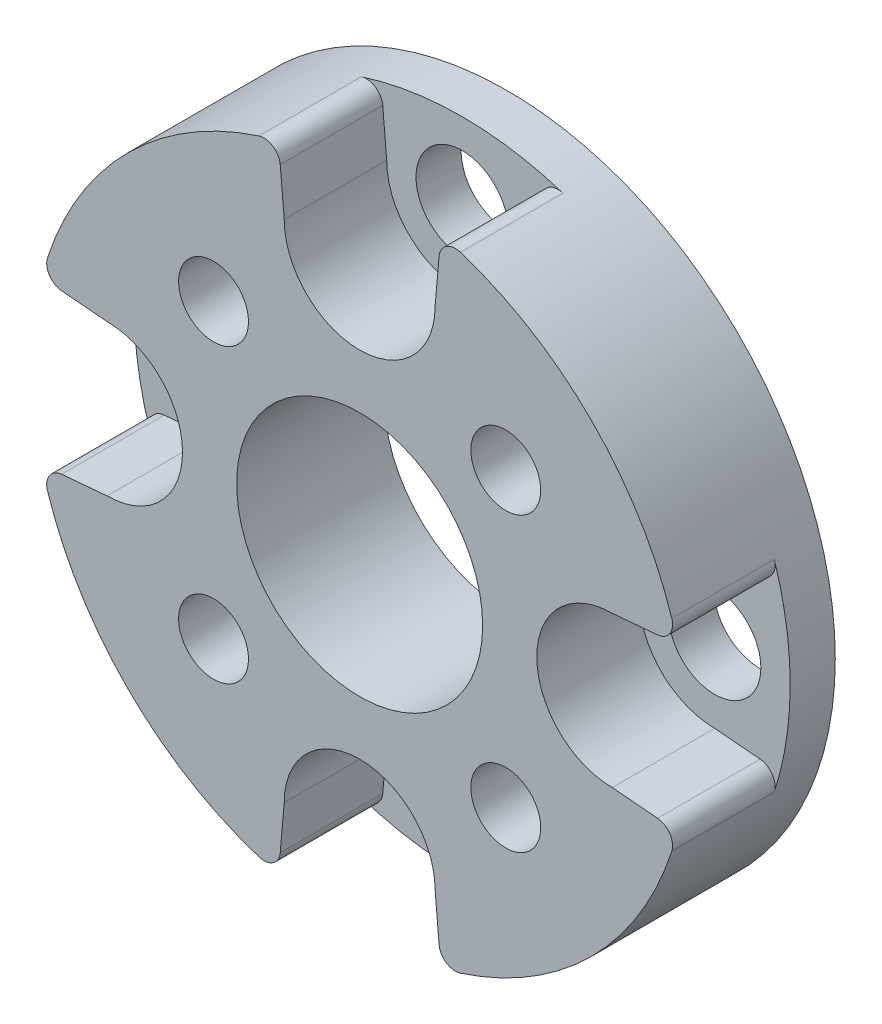
SolidWorks part; units mm, degrees
material "6061 Alloy"
ref_plane "Front Plane" through (0, 0, 0) normal (0, 0, 1) x (1, 0, 0)
ref_plane "Top Plane" through (0, 0, 0) normal (0, 1, 0) x (1, 0, 0)
ref_plane "Right Plane" through (0, 0, 0) normal (1, 0, 0) x (0, 0, -1)
sketch "Sketch1" plane through (0, 0, 0) normal (0, 0, 1) x (1, 0, 0)
  circle A0 centre (0, 0) radius 12.7
  circle A1 centre (0, 0) radius 4.7625
  dimension "D1" = 25.4
  dimension "D2" = 9.525
extrude "Boss-Extrude1" add sketch "Sketch1" along normal mid plane 5.715
hole_wizard "#6-32 Tapped Hole1" positions "Sketch4" profile "Sketch3" tap size "#6-32" standard "Ansi Inch" end condition up to next
sketch "Sketch4" plane through (0, 0, 2.8575) normal (0, 0, 1) x (1, 0, 0)
  line L0 (0, 0) -> (5.6569, 5.6569) construction
  line L2 (0, 0) -> (9.779, 0) construction
  point P0 (5.6569, 5.6569)
  point P19 (5.6569, -5.6569)
  point P20 (-5.6569, -5.6569)
  point P21 (-5.6569, 5.6569)
  dimension "D1" = 8
  dimension "D2" = 45
  dimension "D3" = 9.779
  dimension "D4" = 4
sketch "Sketch3" plane through (5.6569, 5.6569, 2.8575) normal (1, 0, 0) x (0, -1, 0)
  line L0 (0, 0) -> (0, 5.715)
  line L1 (0, 5.715) -> (1.3525, 5.715)
  line L2 (1.3525, 5.715) -> (1.3525, 0)
  line L5 (1.3525, 0) -> (0, 0)
  line L11 (0, -6.35) -> (0, 107.95) construction
  dimension "Thru Tap Drill Dia." = 2.7051
  dimension "Thru Tap Drill Depth" = 5.715
cosmetic thread "Hole Thread1" parameters "D2"=3.5052
cosmetic thread "Hole Thread2" parameters "D2"=3.5052
cosmetic thread "Hole Thread3" parameters "D2"=3.5052
cosmetic thread "Hole Thread4" parameters "D2"=3.5052
sketch "Sketch5" plane through (0, 0, 2.8575) normal (0, 0, 1) x (1, 0, 0)
  line L0 (0, 0) -> (9.779, 0) construction
  line L1 (9.779, 2.921) -> (12.3052, 3.142)
  line L2 (9.779, -2.921) -> (12.3052, -3.142)
  line L3 (2.921, -9.779) -> (3.142, -12.3052)
  line L4 (-2.921, -9.779) -> (-3.142, -12.3052)
  line L5 (-9.779, -2.921) -> (-12.3052, -3.142)
  line L6 (-9.779, 2.921) -> (-12.3052, 3.142)
  line L7 (-2.921, 9.779) -> (-3.142, 12.3052)
  line L8 (2.921, 9.779) -> (3.142, 12.3052)
  arc A0 (9.779, 2.921) -> (9.779, -2.921) centre (9.779, 0) ccw
  circle A1 centre (0, 0) radius 12.7 construction
  arc A2 (12.3052, -3.142) -> (12.3052, 3.142) centre (0, 0) ccw
  arc A3 (2.921, -9.779) -> (-2.921, -9.779) centre (0, -9.779) ccw
  arc A4 (-3.142, -12.3052) -> (3.142, -12.3052) centre (0, 0) ccw
  arc A5 (-9.779, -2.921) -> (-9.779, 2.921) centre (-9.779, 0) ccw
  arc A6 (-12.3052, 3.142) -> (-12.3052, -3.142) centre (0, 0) ccw
  arc A7 (-2.921, 9.779) -> (2.921, 9.779) centre (0, 9.779) ccw
  arc A8 (3.142, 12.3052) -> (-3.142, 12.3052) centre (0, 0) ccw
  dimension "D1" = 9.779
  dimension "D3" = 5.842
  dimension "D4" = 5
  dimension "D2" = 4
extrude "Cut-Extrude1" cut sketch "Sketch5" against normal blind 3.9688
hole_wizard "9/64 (0.14063) Diameter Hole1" positions "Sketch9" profile "Sketch8" hole size "9/64" standard "Ansi Inch" end condition up to next
sketch "Sketch9" plane through (0, 0, -1.1113) normal (0, 0, 1) x (1, 0, 0)
  point P0 (0, 9.779)
  point P1 (-9.779, 0)
  point P4 (0, -9.779)
  point P7 (9.779, 0)
sketch "Sketch8" plane through (0, 9.779, -1.1113) normal (1, 0, 0) x (0, -1, 0)
  line L0 (0, 0) -> (0, 1.7462)
  line L1 (0, 1.7462) -> (1.786, 1.7462)
  line L2 (1.786, 1.7462) -> (1.786, 0)
  line L5 (1.786, 0) -> (0, 0)
  line L11 (0, -6.35) -> (0, 107.95) construction
  dimension "Thru Hole Dia." = 3.572
  dimension "Thru Hole Depth" = 1.7462
fillet "Fillet1" radius 0.635 8 edges at (12.3052, -3.142, 0.8731) (12.3052, 3.142, 0.8731) (3.142, -12.3052, 0.8731) (-3.142, -12.3052, 0.8731) (-12.3052, 3.142, 0.8731) (-12.3052, -3.142, 0.8731) (3.142, 12.3052, 0.8731) (-3.142, 12.3052, 0.8731)
